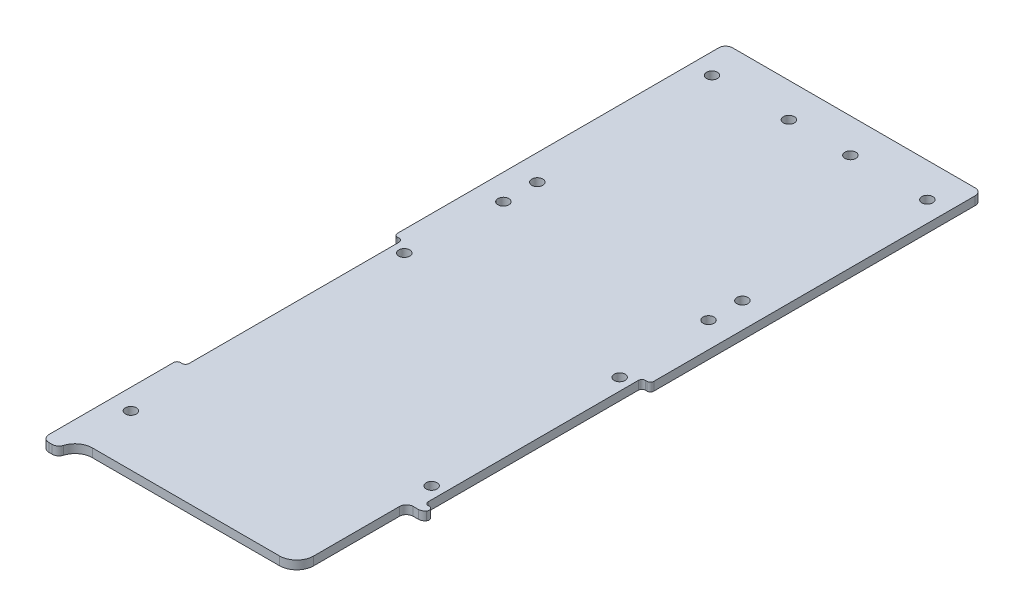
SolidWorks part; units mm, degrees
ref_plane "Front Plane" through (0, 0, 0) normal (0, 0, 1) x (1, 0, 0)
ref_plane "Top Plane" through (0, 0, 0) normal (0, 1, 0) x (1, 0, 0)
ref_plane "Right Plane" through (0, 0, 0) normal (1, 0, 0) x (0, 0, -1)
sketch "Sketch1" plane through (0, 0, 0) normal (0, 1, 0) x (1, 0, 0)
  line L0 (-39.9997, 0) -> (-39.9997, 114.3) construction
  line L1 (-47.625, 127) -> (47.625, 127)
  line L2 (-47.625, 127) -> (-47.625, -127)
  line L3 (-47.625, -127) -> (47.625, -127)
  line L4 (47.625, 127) -> (47.625, -127)
  line L5 (-47.625, 127) -> (47.625, -127) construction
  line L6 (-47.625, -127) -> (47.625, 127) construction
  line L7 (0, 0) -> (0, 127) construction
  line L8 (-39.9997, 0) -> (-39.9997, -101.6) construction
  line L9 (-39.9997, 0) -> (0, 0) construction
  line L10 (-41.275, -127) -> (-41.275, -120.65)
  line L11 (-41.275, -120.65) -> (41.275, -120.65)
  line L12 (41.275, -120.65) -> (41.275, -127)
  line L13 (-39.9997, 114.3) -> (-11.4247, 114.3) construction
  line L14 (39.9997, 114.3) -> (11.4247, 114.3) construction
  circle A0 centre (-39.9997, 114.3) radius 2.032
  circle A1 centre (-39.9997, 0) radius 2.032
  circle A2 centre (-39.9997, -101.6) radius 2.032
  circle A3 centre (39.9997, -101.6) radius 2.032
  circle A4 centre (39.9997, 0) radius 2.032
  circle A5 centre (39.9997, 114.3) radius 2.032
  circle A6 centre (-11.4247, 114.3) radius 2.032
  circle A7 centre (11.4247, 114.3) radius 2.032
  circle A8 centre (-39.9997, -69.85) radius 2.032
  circle A9 centre (39.9997, -69.85) radius 2.032
  point P0 (0, 0)
  dimension "D4" = 4.064
  dimension "D10" = 28.575
  dimension "D1" = 95.25
  dimension "D2" = 254
  dimension "D3" = 7.6253
  dimension "D5" = 12.7
  dimension "D6" = 25.4
  dimension "D7" = 6.35
  dimension "D8" = 6.35
  dimension "D9" = 6.35
  dimension "D11" = 69.85
extrude "Boss-Extrude1" add sketch "Sketch1" along normal blind 3.175 contours L4 L1 L2 L3 A4 A0 A1 A2 A3 A5 | A8 | A3 region at (0, 0, -2.6944) region at (39.9997, 0, 101.6) region at (-39.9997, 0, 69.85)
fillet "Fillet1" radius 2.54 4 edges at (-47.625, 1.5875, -127) (47.625, 1.5875, -127) (47.625, 1.5875, 127) (-47.625, 1.5875, 127)
fillet "Fillet2" radius 2.54 2 edges at (41.275, 1.5875, 127) (-41.275, 1.5875, 127)
fillet "Fillet3" radius 6.35 2 edges at (41.275, 1.5875, 120.65) (-41.275, 1.5875, 120.65)
sketch "Sketch2" plane through (0, 0, 0) normal (0, -1, 0) x (1, 0, 0)
  line L1 (43.815, 127) -> (45.085, 127) construction
  line L2 (40.6451, 123.5787) -> (40.6451, 79.8881)
  line L3 (40.6451, 79.8881) -> (47.625, 79.8881)
  line L11 (47.625, -124.46) -> (47.625, 124.46) construction
  line L12 (43.815, 127) -> (45.085, 127)
  line L13 (47.625, 79.8881) -> (47.625, 124.46)
  arc A0 (35.2956, 120.65) -> (41.3809, 125.1857) centre (35.2956, 127) ccw construction
  arc A1 (43.815, 127) -> (41.3809, 125.1857) centre (43.815, 124.46) ccw construction
  arc A2 (47.625, 124.46) -> (45.085, 127) centre (45.085, 124.46) ccw construction
  arc A3 (40.6451, 123.5787) -> (41.3809, 125.1857) centre (35.2956, 127) ccw
  arc A4 (43.815, 127) -> (41.3809, 125.1857) centre (43.815, 124.46) ccw
  arc A5 (47.625, 124.46) -> (45.085, 127) centre (45.085, 124.46) ccw
  dimension "D2" = 47.1119
  dimension "D1" = 6.9799
extrude "Cut-Extrude1" cut sketch "Sketch2" against normal through all
fillet "Fillet4" radius 6.35 1 edges at (40.6451, 1.5875, 123.5787)
fillet "Fillet5" radius 2.54 2 edges at (47.625, 1.5875, 79.8881) (40.6451, 1.5875, 79.8881)
sketch "Sketch3" plane through (0, 0, 0) normal (0, -1, 0) x (1, 0, 0)
  line L0 (-36.2994, -49.7791) -> (-39.9062, -49.7791) construction
  line L1 (-40.4142, -49.276) -> (-40.4142, -45.7043) construction
  line L2 (-35.7914, -45.7043) -> (-35.7914, -49.276) construction
  line L3 (-39.9062, -45.2013) -> (-36.2994, -45.2013) construction
  line L4 (-36.2994, -37.2027) -> (-39.9062, -37.2027) construction
  line L5 (-35.7914, -33.1279) -> (-35.7914, -36.6996) construction
  line L6 (-40.4142, -36.6996) -> (-40.4142, -33.1279) construction
  line L7 (-39.9062, -32.6249) -> (-36.2994, -32.6249) construction
  line L8 (36.2938, -32.6249) -> (39.9006, -32.6249) construction
  line L9 (40.4086, -33.1279) -> (40.4086, -36.6996) construction
  line L10 (39.9006, -37.2027) -> (36.2938, -37.2027) construction
  line L11 (35.7858, -36.6996) -> (35.7858, -33.1279) construction
  line L12 (36.2938, -45.2013) -> (39.9006, -45.2013) construction
  line L13 (35.7858, -49.276) -> (35.7858, -45.7043) construction
  line L14 (40.4086, -45.7043) -> (40.4086, -49.276) construction
  line L15 (39.9006, -49.7791) -> (36.2938, -49.7791) construction
  line L16 (-36.2994, -49.7791) -> (-39.9062, -49.7791)
  line L17 (-40.4142, -49.276) -> (-40.4142, -45.7043)
  line L18 (-35.7914, -45.7043) -> (-35.7914, -49.276)
  line L19 (-39.9062, -45.2013) -> (-36.2994, -45.2013)
  line L20 (-36.2994, -37.2027) -> (-39.9062, -37.2027)
  line L21 (-35.7914, -33.1279) -> (-35.7914, -36.6996)
  line L22 (-40.4142, -36.6996) -> (-40.4142, -33.1279)
  line L23 (-39.9062, -32.6249) -> (-36.2994, -32.6249)
  line L24 (36.2938, -32.6249) -> (39.9006, -32.6249)
  line L25 (40.4086, -33.1279) -> (40.4086, -36.6996)
  line L26 (39.9006, -37.2027) -> (36.2938, -37.2027)
  line L27 (35.7858, -36.6996) -> (35.7858, -33.1279)
  line L28 (36.2938, -45.2013) -> (39.9006, -45.2013)
  line L29 (35.7858, -49.276) -> (35.7858, -45.7043)
  line L30 (40.4086, -45.7043) -> (40.4086, -49.276)
  line L31 (39.9006, -49.7791) -> (36.2938, -49.7791)
  line L32 (-47.625, -25.836) -> (47.625, -25.836)
  line L33 (-47.625, -124.46) -> (-47.625, 124.46) construction
  line L34 (47.625, -124.46) -> (47.625, 77.3481) construction
  line L35 (0, -25.836) -> (0, -56.0686) construction
  line L1362 (-40.4142, -34.9138) -> (-35.7914, -34.9138)
  line L1857 (-38.1028, -32.6249) -> (-38.1028, -37.2027)
  line L1858 (-38.1028, -45.2013) -> (-38.1028, -49.7791)
  line L1859 (-40.4142, -47.4902) -> (-35.7914, -47.4902)
  circle A0 centre (-38.1028, -34.9138) radius 2.032
  circle A1 centre (-38.1028, -47.4902) radius 2.032
  circle A2 centre (38.1028, -47.4902) radius 2.032
  circle A3 centre (38.1028, -34.9138) radius 2.032
  ellipse E0 centre (-39.9062, -45.7043) end of major axis (-39.3982, -45.7043) minor radius 0.5031 (-39.9062, -45.2013) -> (-40.4142, -45.7043) ccw construction
  ellipse E1 centre (-39.9062, -49.276) end of major axis (-39.3982, -49.276) minor radius 0.5031 (-40.4142, -49.276) -> (-39.9062, -49.7791) ccw construction
  ellipse E6 centre (-36.2994, -49.276) end of major axis (-35.7914, -49.276) minor radius 0.5031 (-36.2994, -49.7791) -> (-35.7914, -49.276) ccw construction
  ellipse E7 centre (-36.2994, -45.7043) end of major axis (-35.7914, -45.7043) minor radius 0.5031 (-35.7914, -45.7043) -> (-36.2994, -45.2013) ccw construction
  ellipse E8 centre (-39.9062, -36.6996) end of major axis (-39.3982, -36.6996) minor radius 0.5031 (-40.4142, -36.6996) -> (-39.9062, -37.2027) ccw construction
  ellipse E9 centre (-36.2994, -36.6996) end of major axis (-35.7914, -36.6996) minor radius 0.5031 (-36.2994, -37.2027) -> (-35.7914, -36.6996) ccw construction
  ellipse E10 centre (-36.2994, -33.1279) end of major axis (-35.7914, -33.1279) minor radius 0.5031 (-35.7914, -33.1279) -> (-36.2994, -32.6249) ccw construction
  ellipse E11 centre (-39.9062, -33.1279) end of major axis (-39.3982, -33.1279) minor radius 0.5031 (-39.9062, -32.6249) -> (-40.4142, -33.1279) ccw construction
  ellipse E12 centre (39.9006, -33.1279) end of major axis (40.4086, -33.1279) minor radius 0.5031 (40.4086, -33.1279) -> (39.9006, -32.6249) ccw construction
  ellipse E13 centre (36.2938, -33.1279) end of major axis (36.8018, -33.1279) minor radius 0.5031 (36.2938, -32.6249) -> (35.7858, -33.1279) ccw construction
  ellipse E14 centre (39.9006, -36.6996) end of major axis (40.4086, -36.6996) minor radius 0.5031 (39.9006, -37.2027) -> (40.4086, -36.6996) ccw construction
  ellipse E15 centre (36.2938, -36.6996) end of major axis (36.8018, -36.6996) minor radius 0.5031 (35.7858, -36.6996) -> (36.2938, -37.2027) ccw construction
  ellipse E16 centre (36.2938, -45.7043) end of major axis (36.8018, -45.7043) minor radius 0.5031 (36.2938, -45.2013) -> (35.7858, -45.7043) ccw construction
  ellipse E17 centre (36.2938, -49.276) end of major axis (36.8018, -49.276) minor radius 0.5031 (35.7858, -49.276) -> (36.2938, -49.7791) ccw construction
  ellipse E18 centre (39.9006, -45.7043) end of major axis (40.4086, -45.7043) minor radius 0.5031 (40.4086, -45.7043) -> (39.9006, -45.2013) ccw construction
  ellipse E19 centre (39.9006, -49.276) end of major axis (40.4086, -49.276) minor radius 0.5031 (39.9006, -49.7791) -> (40.4086, -49.276) ccw construction
  ellipse E20 centre (-39.9062, -45.7043) end of major axis (-39.3982, -45.7043) minor radius 0.5031 (-39.9062, -45.2013) -> (-40.4142, -45.7043) ccw
  ellipse E21 centre (-39.9062, -49.276) end of major axis (-39.3982, -49.276) minor radius 0.5031 (-40.4142, -49.276) -> (-39.9062, -49.7791) ccw
  ellipse E22 centre (-36.2994, -49.276) end of major axis (-35.7914, -49.276) minor radius 0.5031 (-36.2994, -49.7791) -> (-35.7914, -49.276) ccw
  ellipse E23 centre (-36.2994, -45.7043) end of major axis (-35.7914, -45.7043) minor radius 0.5031 (-35.7914, -45.7043) -> (-36.2994, -45.2013) ccw
  ellipse E24 centre (-39.9062, -36.6996) end of major axis (-39.3982, -36.6996) minor radius 0.5031 (-40.4142, -36.6996) -> (-39.9062, -37.2027) ccw
  ellipse E25 centre (-36.2994, -36.6996) end of major axis (-35.7914, -36.6996) minor radius 0.5031 (-36.2994, -37.2027) -> (-35.7914, -36.6996) ccw
  ellipse E26 centre (-36.2994, -33.1279) end of major axis (-35.7914, -33.1279) minor radius 0.5031 (-35.7914, -33.1279) -> (-36.2994, -32.6249) ccw
  ellipse E27 centre (-39.9062, -33.1279) end of major axis (-39.3982, -33.1279) minor radius 0.5031 (-39.9062, -32.6249) -> (-40.4142, -33.1279) ccw
  ellipse E28 centre (39.9006, -33.1279) end of major axis (40.4086, -33.1279) minor radius 0.5031 (40.4086, -33.1279) -> (39.9006, -32.6249) ccw
  ellipse E29 centre (36.2938, -33.1279) end of major axis (36.8018, -33.1279) minor radius 0.5031 (36.2938, -32.6249) -> (35.7858, -33.1279) ccw
  ellipse E30 centre (39.9006, -36.6996) end of major axis (40.4086, -36.6996) minor radius 0.5031 (39.9006, -37.2027) -> (40.4086, -36.6996) ccw
  ellipse E31 centre (36.2938, -36.6996) end of major axis (36.8018, -36.6996) minor radius 0.5031 (35.7858, -36.6996) -> (36.2938, -37.2027) ccw
  ellipse E32 centre (36.2938, -45.7043) end of major axis (36.8018, -45.7043) minor radius 0.5031 (36.2938, -45.2013) -> (35.7858, -45.7043) ccw
  ellipse E33 centre (36.2938, -49.276) end of major axis (36.8018, -49.276) minor radius 0.5031 (35.7858, -49.276) -> (36.2938, -49.7791) ccw
  ellipse E34 centre (39.9006, -45.7043) end of major axis (40.4086, -45.7043) minor radius 0.5031 (40.4086, -45.7043) -> (39.9006, -45.2013) ccw
  ellipse E35 centre (39.9006, -49.276) end of major axis (40.4086, -49.276) minor radius 0.5031 (39.9006, -49.7791) -> (40.4086, -49.276) ccw
  dimension "D2" = 4.064
extrude "Cut-Extrude2" cut sketch "Sketch3" against normal through all contours A0 | A1 | A2 | A3
sketch "Sketch4" plane through (0, 3.175, 0) normal (0, 1, 0) x (1, 0, 0)
  line L11 (-47.625, 124.46) -> (-47.625, -124.46) construction
  line L12 (-47.625, -76.835) -> (-44.45, -76.835)
  line L13 (-47.625, -76.835) -> (-47.625, 3.81)
  line L15 (-47.625, 3.81) -> (-44.45, 3.81)
  line L16 (-44.45, -76.835) -> (-44.45, 3.81)
  line L17 (47.625, 124.46) -> (47.625, -77.3481) construction
  line L18 (47.625, -76.835) -> (44.45, -76.835)
  line L19 (47.625, -76.835) -> (47.625, 3.81)
  line L20 (47.625, 3.81) -> (44.45, 3.81)
  line L45 (44.45, -76.835) -> (44.45, 3.81)
  line L47 (43.1851, -79.8881) -> (45.085, -79.8881) construction
  dimension "D1" = 3.175
  dimension "D2" = 80.645
  dimension "D3" = 3.0531
extrude "Cut-Extrude3" cut sketch "Sketch4" against normal through all and the other way through all
fillet "Fillet6" radius 1.27 8 edges at (-44.45, 1.5875, -3.81) (-47.625, 1.5875, -3.81) (-47.625, 1.5875, 76.835) (-44.45, 1.5875, 76.835) (44.45, 1.5875, 76.835) (47.625, 1.5875, 76.835) (44.45, 1.5875, -3.81) (47.625, 1.5875, -3.81)
